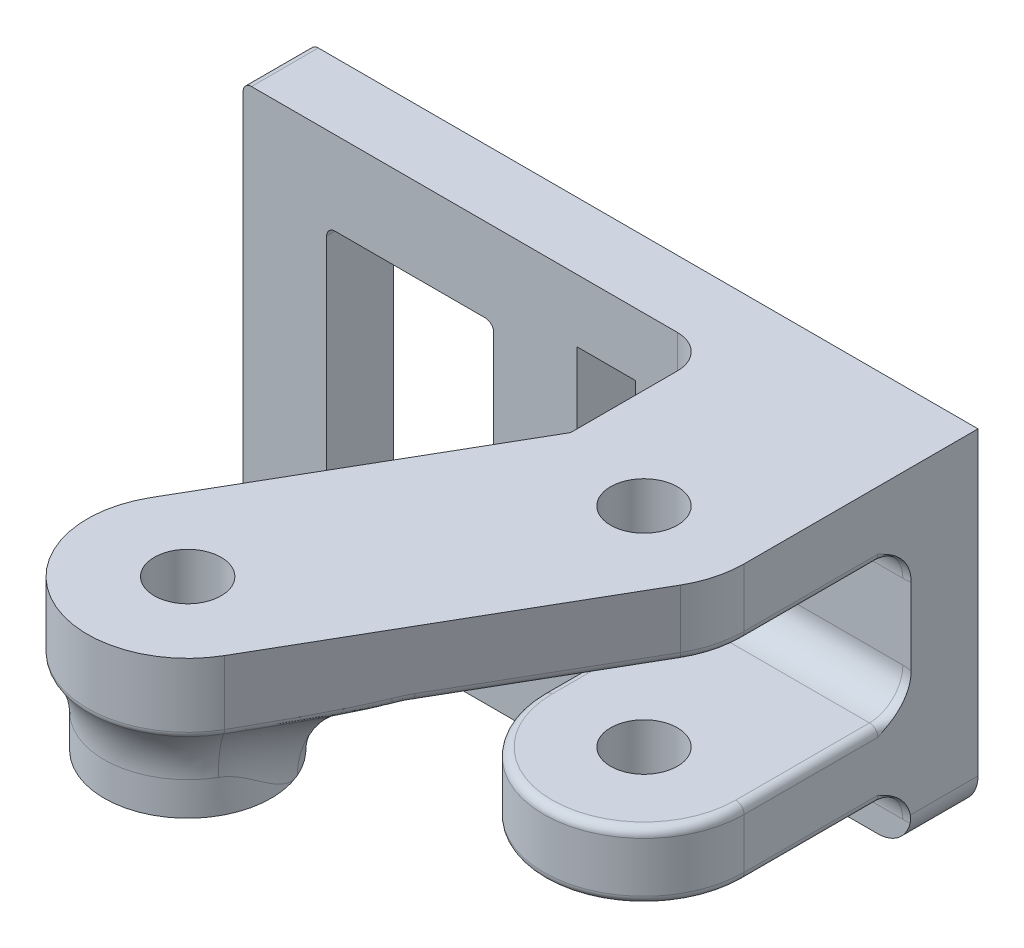
SolidWorks part; units mm, degrees
ref_plane "Front Plane" through (0, 0, 0) normal (0, 0, 1) x (1, 0, 0)
ref_plane "Top Plane" through (0, 0, 0) normal (0, 1, 0) x (1, 0, 0)
ref_plane "Right Plane" through (0, 0, 0) normal (1, 0, 0) x (0, 0, -1)
sketch "Sketch1" plane through (0, 0, 0) normal (0, 0, 1) x (1, 0, 0)
  line L1 (-21.566, 10.3356) -> (18.434, 10.3356)
  line L2 (-21.566, 10.3356) -> (-21.566, -14.6644)
  line L3 (-21.566, -14.6644) -> (18.434, -14.6644)
  line L4 (18.434, 10.3356) -> (18.434, -14.6644)
  dimension "D1" = 40
  dimension "D2" = 25
extrude "Boss-Extrude1" add sketch "Sketch1" along normal blind 4
sketch "Sketch2" plane through (0, 0, 4) normal (0, 0, 1) x (1, 0, 0)
  line L1 (18.434, 10.3356) -> (6.434, 10.3356)
  line L2 (18.434, 10.3356) -> (18.434, 6.3356)
  line L3 (18.434, 6.3356) -> (6.434, 6.3356)
  line L4 (6.434, 10.3356) -> (6.434, 6.3356)
  dimension "D1" = 12
  dimension "D2" = 4
extrude "Boss-Extrude2" add sketch "Sketch2" along normal blind 35
sketch "Sketch3" plane through (0, 10.3356, 0) normal (0, 1, 0) x (1, 0, 0)
  line L0 (6.434, -4) -> (-21.566, -4) construction
  line L1 (6.434, -39) -> (6.434, -4) construction
  circle A0 centre (12.434, -14) radius 2
  dimension "D1" = 4
  dimension "D2" = 10
  dimension "D3" = 6
extrude "Cut-Extrude1" cut sketch "Sketch3" against normal through all
sketch "Sketch4" plane through (0, 10.3356, 0) normal (0, 1, 0) x (1, 0, 0)
  line L0 (12.434, -14) -> (12.434, -31.3205) construction
  line L1 (12.434, -31.3205) -> (-7.2938, -31.3205) construction
  line L2 (12.434, -14) -> (2.434, -31.3205) construction
  line L3 (12.434, -14) -> (-2.4928, -5.382) construction
  line L4 (-2.7621, -28.3205) -> (7.2379, -11)
  line L5 (12.434, -14) -> (23.3301, -20.2909) construction
  line L6 (7.6302, -34.3205) -> (17.6302, -17)
  line L7 (18.434, -14) -> (18.434, -39)
  line L8 (18.434, -39) -> (6.434, -39)
  line L9 (6.434, -39) -> (6.434, -35.7926)
  line L10 (6.434, -39) -> (6.434, -4) construction
  line L11 (6.434, -35.7926) -> (7.6302, -34.3205)
  line L12 (17.6302, -17) -> (18.434, -14)
  circle A0 centre (2.434, -31.3205) radius 2
  arc A1 (-2.7621, -28.3205) -> (7.6302, -34.3205) centre (2.434, -31.3205) ccw
  arc A3 (17.6302, -17) -> (7.2379, -11) centre (12.434, -14) ccw
  line M16 (6.434, -4) -> (6.434, -39)
  dimension "D3" = 4
  dimension "D4" = 12
  dimension "D1" = 10
  dimension "D2" = 20
extrude "Boss-Extrude3" add sketch "Sketch4" against normal blind 4 contours L4 A1 A0 M16
sketch "Sketch5" plane through (0, 10.3356, 0) normal (0, 1, 0) x (1, 0, 0)
  line L0 (17.6302, -17) -> (7.6302, -34.3205)
  line L1 (18.434, -14) -> (18.434, -39)
  line L2 (18.434, -39) -> (6.434, -39)
  line L3 (6.434, -39) -> (6.434, -35.7926)
  arc A0 (6.434, -35.7926) -> (7.6302, -34.3205) centre (2.434, -31.3205) ccw
  arc A1 (17.6302, -17) -> (18.434, -14) centre (12.434, -14) ccw
extrude "Cut-Extrude3" cut sketch "Sketch5" against normal through all
sketch "Sketch6" plane through (0, 6.3356, 0) normal (0, -1, 0) x (1, 0, 0)
  circle A0 centre (2.434, 31.3205) radius 5
  circle A1 centre (2.434, 31.3205) radius 2
  dimension "D1" = 10
  dimension "D2" = 4
extrude "Boss-Extrude4" add sketch "Sketch6" along normal blind 5
fillet "Fillet1" radius 5 1 edges at (-2.566, 6.3356, 31.3205)
fillet "Fillet2" radius 0.5 8 edges at (18.2296, 6.3356, 15.5529) (18.434, 6.3356, 9) (6.434, 6.3356, 8.1962) (3.8359, 6.3356, 16.8923) (-0.7621, 6.3356, 24.8564) (-0.566, 6.3356, 36.5167) (9.6302, 6.3356, 30.8564) (14.6302, 6.3356, 22.1962)
sketch "Sketch7" plane through (0, 0, 4) normal (0, 0, 1) x (1, 0, 0)
  line L0 (18.434, -14.6644) -> (18.434, 6.8356) construction
  line L1 (18.434, -6.1644) -> (6.434, -6.1644)
  line L2 (18.434, -6.1644) -> (18.434, -2.1644)
  line L3 (18.434, -2.1644) -> (6.434, -2.1644)
  line L4 (6.434, -6.1644) -> (6.434, -2.1644)
  line L5 (6.934, 6.3356) -> (17.934, 6.3356) construction
  dimension "D1" = 12
  dimension "D2" = 4
  dimension "D3" = 8.5
extrude "Boss-Extrude5" add sketch "Sketch7" along normal blind 20
sketch "Sketch8" plane through (0, 10.3356, 0) normal (0, 1, 0) x (1, 0, 0)
  line L0 (12.434, -16) -> (12.434, -12) construction
  circle A0 centre (12.434, -14) radius 2 construction
  circle A1 centre (12.434, -14) radius 2
extrude "Cut-Extrude4" cut sketch "Sketch8" against normal through all
sketch "Sketch10" plane through (0, -6.1644, 0) normal (0, -1, 0) x (1, 0, 0)
  line L0 (6.434, 14) -> (6.434, 24)
  line L1 (6.434, 24) -> (18.434, 24)
  line L2 (18.434, 24) -> (18.434, 14)
  arc A0 (18.434, 14) -> (6.434, 14) centre (12.434, 14) ccw
extrude "Cut-Extrude5" cut sketch "Sketch10" against normal blind 5
fillet "Fillet3" radius 0.5 3 edges at (6.434, -2.1644, 9) (12.434, -2.1644, 20) (18.434, -2.1644, 9)
fillet "Fillet4" radius 0.5 3 edges at (18.434, -6.1644, 9) (12.434, -6.1644, 20) (6.434, -6.1644, 9)
fillet "Fillet5" radius 2 11 edges at (6.434, 8.5856, 4) (6.5805, 6.482, 4) (18.2876, 6.482, 4) (18.2876, -2.3109, 4) (6.5805, -2.3109, 4) (6.434, -4.1644, 4) (6.5805, -6.018, 4) (18.2876, -6.018, 4) (12.434, 6.3356, 4) (12.434, -2.1644, 4) (12.434, -6.1644, 4)
fillet "Fillet6" radius 5 1 edges at (18.434, -14.6644, 2)
sketch "Sketch12" plane through (0, 0, 4) normal (0, 0, 1) x (1, 0, 0)
  line L0 (-21.566, 10.3356) -> (-21.566, -14.6644) construction
  line L1 (-16.566, 5.3356) -> (-6.566, 5.3356)
  line L2 (-16.566, 5.3356) -> (-16.566, -9.6644)
  line L3 (-16.566, -9.6644) -> (-6.566, -9.6644)
  line L4 (-6.566, 5.3356) -> (-6.566, -9.6644)
  line L5 (4.434, 10.3356) -> (-21.566, 10.3356) construction
  line L6 (-21.566, -14.6644) -> (13.434, -14.6644) construction
  line L7 (6.2443, -9.6644) -> (18.434, -9.6644)
  line L8 (18.434, -9.6644) -> (18.434, -14.6644)
  line L12 (-1.566, -14.6644) -> (3.0433, -10.8233)
  line L13 (-1.566, -14.6644) -> (18.434, -14.6644)
  arc A0 (6.2443, -9.6644) -> (3.0433, -10.8233) centre (6.2443, -14.6644) ccw
  dimension "D5" = 5
  dimension "D1" = 5
  dimension "D2" = 5
  dimension "D3" = 5
  dimension "D4" = 10
extrude "Cut-Extrude7" cut sketch "Sketch12" against normal blind 5
fillet "Fillet9" radius 0.5 6 edges at (-6.566, -9.6644, 2) (-16.566, -9.6644, 2) (-16.566, 5.3356, 2) (-6.566, 5.3356, 2) (-21.566, 10.3356, 2) (-21.566, -14.6644, 2)
fillet "Fillet10" radius 2 1 edges at (-1.566, -14.6644, 2)
fillet "Fillet11" radius 2 1 edges at (18.434, -9.6644, 2)
sketch "Sketch13" plane through (0, 0, 4) normal (0, 0, 1) x (1, 0, 0)
  line L0 (18.434, 2.0856) -> (-6.566, 2.0856) construction
  line L1 (18.434, -0.2149) -> (18.434, 4.3861) construction
  line L2 (-6.566, -9.1644) -> (-6.566, 4.8356) construction
  line L4 (-1.566, 6.5856) -> (1.934, 6.5856)
  line L5 (-1.566, 6.5856) -> (-1.566, -2.4144)
  line L6 (-1.566, -2.4144) -> (1.934, -2.4144)
  line L7 (1.934, 6.5856) -> (1.934, -2.4144)
  point P10 (0.184, -2.4144)
  dimension "D1" = 9
  dimension "D2" = 4.5
  dimension "D3" = 3.5
  dimension "D4" = 5
extrude "Cut-Extrude8" cut sketch "Sketch13" against normal through all
